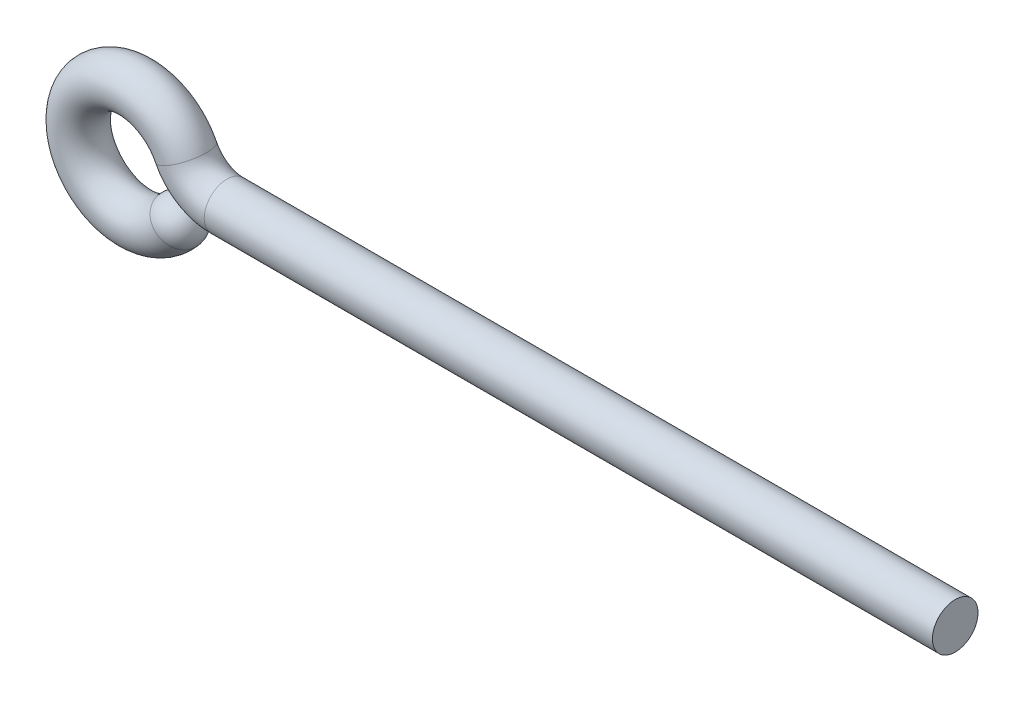
SolidWorks part; units mm, degrees
ref_plane "Front Plane" through (0, 0, 0) normal (0, 0, 1) x (1, 0, 0)
ref_plane "Top Plane" through (0, 0, 0) normal (0, 1, 0) x (1, 0, 0)
ref_plane "Right Plane" through (0, 0, 0) normal (1, 0, 0) x (0, 0, -1)
sketch "Sketch1" plane through (0, 0, 0) normal (0, 0, 1) x (1, 0, 0)
  line L0 (0, 0) -> (-6, 0) construction
  line L1 (-6, 0) -> (-4.0849, -1.607) construction
  line L2 (-1.9689, 0) -> (0, 0)
  arc A0 (-3.7605, 1.1111) -> (-4.0849, -1.607) centre (-6, 0) ccw
  arc A1 (-3.7605, 1.1111) -> (-1.9689, 0) centre (-1.9689, 2) ccw
  point P7 (-3.5, 0)
  dimension "D2" = 2.5
  dimension "D4" = 2
  dimension "D1" = 6
  dimension "D3" = 40
sketch "Sketch2" plane through (0, 0, 0) normal (1, 0, 0) x (0, 0, -1)
  circle A0 centre (0, 0) radius 1
  dimension "D1" = 2
sweep "Sweep1" add profiles "Sketch2" path "Sketch1"
sketch "Sketch3" plane through (0, 0, 0) normal (1, 0, 0) x (0, 0, -1)
  circle A1 centre (0, 0) radius 1
  circle A2 centre (0, 0) radius 1
  dimension "D1" = 0
extrude "Boss-Extrude1" add sketch "Sketch3" along normal blind 30
dome "Dome1" faces to dome 1 distance 1 reverse direction no elliptical dome no face at (-4.0849, -1.607, -1) parameters "D1"=1
